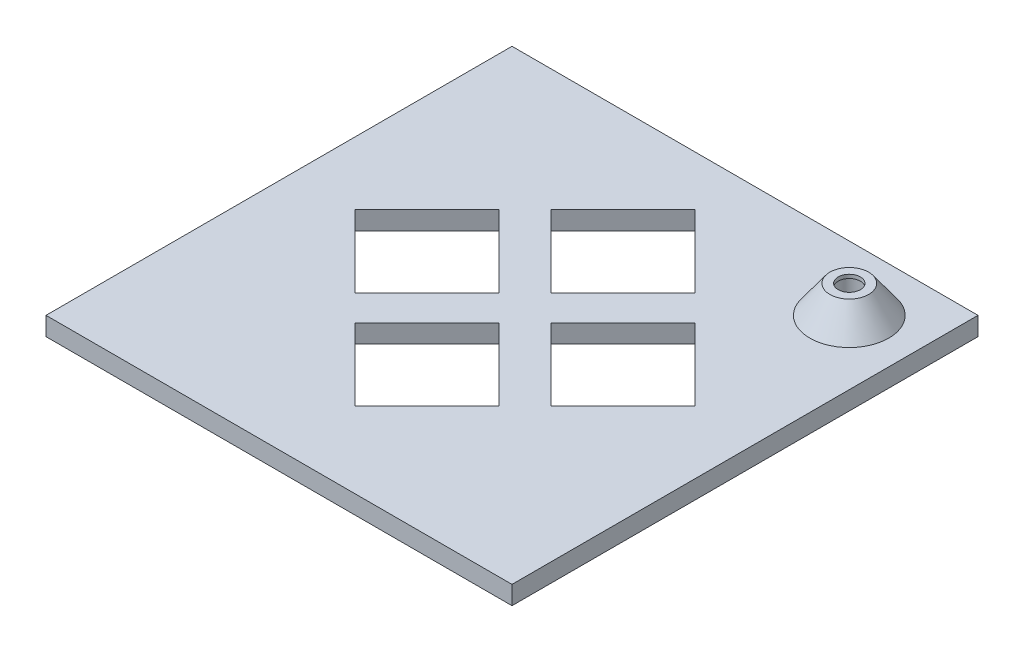
SolidWorks part; units mm, degrees
ref_plane "Front Plane" through (0, 0, 0) normal (0, 0, 1) x (1, 0, 0)
ref_plane "Top Plane" through (0, 0, 0) normal (0, 1, 0) x (1, 0, 0)
ref_plane "Right Plane" through (0, 0, 0) normal (1, 0, 0) x (0, 0, -1)
sketch "Sketch1" plane through (0, 0, 0) normal (0, 1, 0) x (1, 0, 0)
  line L1 (0, 0) -> (126, 0)
  line L2 (0, 0) -> (0, 126)
  line L3 (0, 126) -> (126, 126)
  line L4 (126, 0) -> (126, 126)
  dimension "D1" = 126
  dimension "D2" = 126
extrude "Boss-Extrude1" add sketch "Sketch1" along normal blind 5
sketch "Sketch3" plane through (0, 5, 0) normal (0, 1, 0) x (1, 0, 0)
  line L0 (108.6, 121.1) -> (108.6, 96.1) construction
  circle A0 centre (108.6, 108.6) radius 12.5
extrude "Boss-Extrude2" add sketch "Sketch3" along normal blind 7.5
sketch "Sketch4" plane through (0, 0, 0) normal (0, -1, 0) x (1, 0, 0)
  circle A1 centre (108.6, -108.6) radius 3.45
  dimension "D1" = 6.9
extrude "Cut-Extrude1" cut sketch "Sketch4" against normal blind 11.5
sketch "Sketch6" plane through (0, 12.5, 0) normal (0, 1, 0) x (1, 0, 0)
  line L0 (108.6, 121.1) -> (108.6, 96.1) construction
  circle A0 centre (108.6, 108.6) radius 12.5 construction
  circle A1 centre (108.6, 108.6) radius 3
  dimension "D1" = 6
extrude "Cut-Extrude2" cut sketch "Sketch6" against normal through all
chamfer "Chamfer1" distance 10 angle 36 1 edges at (108.6, 12.5, -96.1) first distance on face at (108.6, 12.5, -96.1)
sketch "Sketch7" plane through (0, 5, 0) normal (0, 1, 0) x (1, 0, 0)
  line L0 (63, 66.5) -> (63, 59.5) construction
  line L1 (70, 66.5) -> (109, 66.5) construction
  line L2 (89.5, 66.5) -> (89.5, 86) construction
  line L3 (63, 66.5) -> (70, 66.5) construction
  line L4 (70, 66.5) -> (89.5, 86)
  line L5 (70, 66.5) -> (89.5, 47)
  line L6 (63, 66.5) -> (56, 66.5) construction
  line L13 (63, 66.5) -> (63, 73.5) construction
  line L14 (89.5, 86) -> (109, 66.5)
  line L15 (89.5, 47) -> (109, 66.5)
  line L16 (63, 73.5) -> (63, 112.5) construction
  line L17 (63, 93) -> (82.5, 93) construction
  line L18 (63, 73.5) -> (82.5, 93)
  line L19 (63, 73.5) -> (43.5, 93)
  line L20 (82.5, 93) -> (63, 112.5)
  line L21 (43.5, 93) -> (63, 112.5)
  line L22 (56, 66.5) -> (17, 66.5) construction
  line L23 (63, 59.5) -> (63, 20.5) construction
  line L24 (36.5, 66.5) -> (36.5, 86) construction
  line L25 (63, 40) -> (43.5, 40) construction
  line L26 (56, 66.5) -> (36.5, 86)
  line L27 (56, 66.5) -> (36.5, 47)
  line L28 (36.5, 86) -> (17, 66.5)
  line L29 (36.5, 47) -> (17, 66.5)
  line L30 (63, 59.5) -> (43.5, 40)
  line L31 (63, 59.5) -> (82.5, 40)
  line L32 (43.5, 40) -> (63, 20.5)
  line L33 (82.5, 40) -> (63, 20.5)
  point P12 (63, 63)
  dimension "D3" = 7
  dimension "D4" = 7
  dimension "D5" = 7
  dimension "D6" = 7
  dimension "D7" = 39
  dimension "D9" = 39
  dimension "D11" = 39
  dimension "D12" = 39
extrude "Cut-Extrude3" cut sketch "Sketch7" against normal through all and the other way through all
